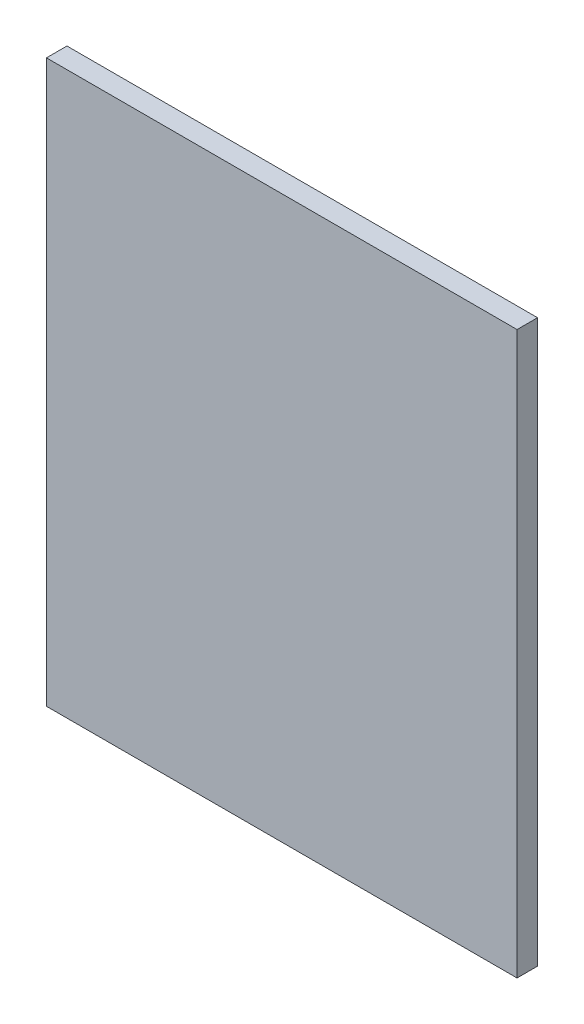
SolidWorks part; units mm, degrees
ref_plane "Front Plane" through (0, 0, 0) normal (0, 0, 1) x (1, 0, 0)
ref_plane "Top Plane" through (0, 0, 0) normal (0, 1, 0) x (1, 0, 0)
ref_plane "Right Plane" through (0, 0, 0) normal (1, 0, 0) x (0, 0, -1)
sketch "Sketch1" plane through (0, 0, 0) normal (0, 0, 1) x (1, 0, 0)
  line L2 (-72.898, 0) -> (-72.898, 173.99)
  line L4 (-72.898, 173.99) -> (72.898, 173.99)
  line L5 (-72.898, 0) -> (72.898, 0)
  line L6 (72.898, 173.99) -> (72.898, 0)
extrude "Boss-Extrude1" add sketch "Sketch1" along normal blind 6.35
